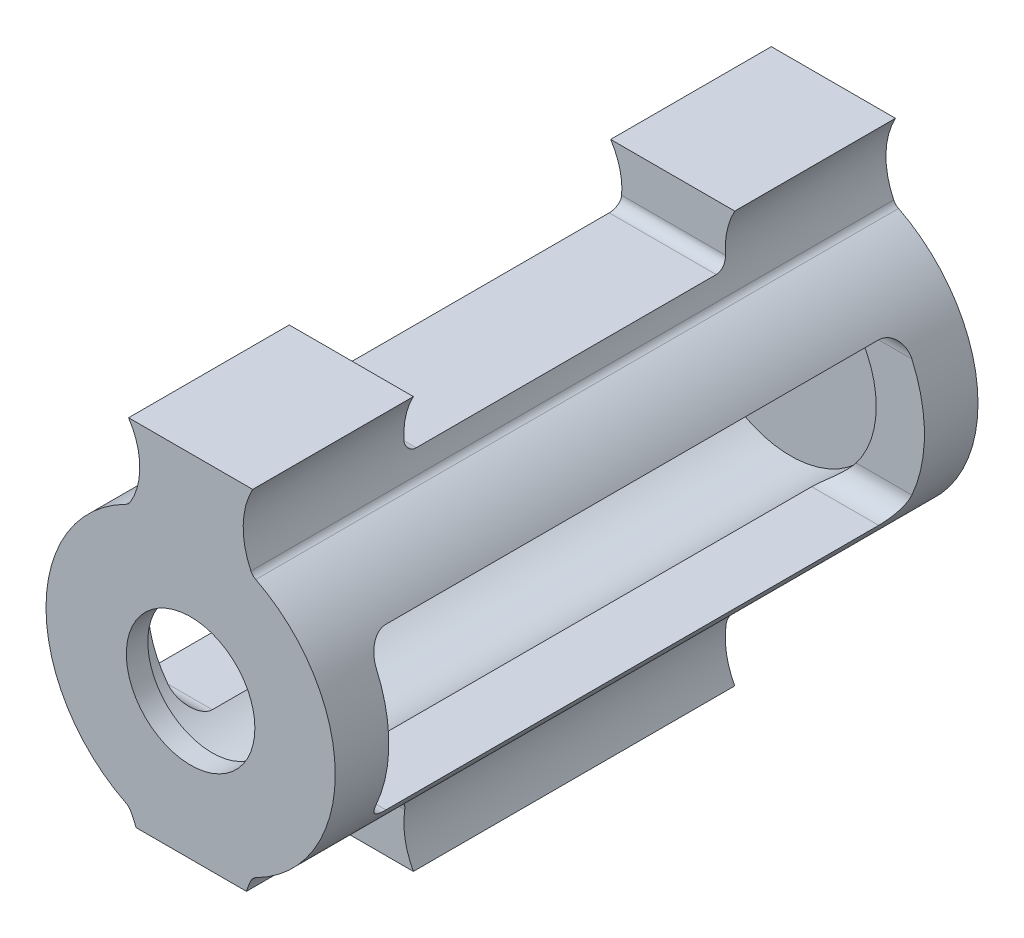
SolidWorks part; units mm, degrees
material "AISI 4130 Steel, annealed at 865C"
ref_plane "Front Plane" through (0, 0, 0) normal (0, 0, 1) x (1, 0, 0)
ref_plane "Top Plane" through (0, 0, 0) normal (0, 1, 0) x (1, 0, 0)
ref_plane "Right Plane" through (0, 0, 0) normal (1, 0, 0) x (0, 0, -1)
other "Center of Mass"
sketch "Sketch1" plane through (0, 0, 0) normal (0, 0, 1) x (1, 0, 0)
  line L8 (-34.29, 0) -> (-52.5688, 0)
  line L9 (-14.7129, 48.7531) -> (14.7129, 48.7531)
  line L10 (-14.7129, -48.7531) -> (14.7129, -48.7531)
  circle A0 centre (0, 0) radius 34.29
  circle A1 centre (0, 0) radius 22.86
  arc A2 (-14.7129, 48.7531) -> (-14.7129, 30.9731) centre (-28.2065, 39.8631) cw
  arc A3 (14.7129, 48.7531) -> (14.7129, 30.9731) centre (31.1324, 39.8631) ccw
  arc A4 (14.7129, -48.7531) -> (14.7129, -30.9731) centre (31.1324, -39.8631) cw
  arc A5 (-14.7129, -48.7531) -> (-14.7129, -30.9731) centre (-28.2065, -39.8631) ccw
  point P9 (0, 48.7531)
  dimension "D1" = 68.58
  dimension "D3" = 17.78
  dimension "D2" = 11.43
extrude "Boss-Extrude1" add sketch "Sketch1" along normal blind 139.7 and the other way blind 12.7 contours A3 L9 A2 A0 | A0 A1 | A5 L10 A4 A0 region at (0.1638, 41.1103, 0) region at (0, 33.3201, 0) region at (0.1638, -41.1103, 0)
ref_plane "Plane2" through (-14.7129, 0, 0) normal (1, 0, 0) x (0, 0, -1)
sketch "Sketch3" plane through (-14.7129, 0, 0) normal (1, 0, 0) x (0, 0, -1)
  line L5 (-25.4, 48.7531) -> (-25.4, 36.0531)
  line L6 (-25.4, 48.7531) -> (-101.6, 48.7531)
  line L7 (-25.4, 36.0531) -> (-101.6, 36.0531)
  line L8 (-101.6, 48.7531) -> (-101.6, 36.0531)
  line L9 (-139.7, 48.7531) -> (12.7, 48.7531) construction
  line L10 (-139.7, 30.9731) -> (12.7, 30.9731) construction
  line L11 (-101.6, -34.5291) -> (-139.7, -34.5291)
  line L12 (-139.7, -30.9731) -> (-139.7, -48.7531) construction
  line L13 (-139.7, -34.5291) -> (-139.7, -48.7531)
  line L14 (-139.7, -48.7531) -> (-101.6, -48.7531)
  line L15 (-139.7, -48.7531) -> (12.7, -48.7531) construction
  line L16 (-101.6, -48.7531) -> (-101.6, -34.5291)
  line L17 (-139.7, -30.9731) -> (12.7, -30.9731) construction
  line L18 (-63.5, 48.7531) -> (-63.5, 62.3768)
  line L19 (12.7, -34.5291) -> (12.7, -48.7531)
  line L20 (12.7, -48.7531) -> (-25.4, -48.7531)
  line L21 (-25.4, -48.7531) -> (-25.4, -34.5291)
  line L22 (-25.4, -34.5291) -> (12.7, -34.5291)
  dimension "D1" = 38.1
  dimension "D2" = 38.1
  dimension "D3" = 12.7
  dimension "D4" = 5.08
  dimension "D5" = 3.556
  dimension "D6" = 38.1
extrude "Cut-Extrude1" cut sketch "Sketch3" against normal through all both and the other way through all contours L6 L8 L7 L5 | L14 L16 L11 L13 | L22 L21 L20 L19 region at (-14.7129, 42.4031, 63.5) region at (-14.7129, -41.6411, 120.65) region at (-14.7129, -41.6411, 6.35)
fillet "Fillet1" radius 2.54 4 edges at (0.1752, 36.0531, 25.4) (0.1752, 36.0531, 101.6) (0.1427, -34.5291, 101.6) (0.1427, -34.5291, 25.4)
fillet "Fillet2" radius 2.54 4 edges at (-14.7129, 30.9731, 63.5) (14.7129, 30.9731, 63.5) (14.7129, -30.9731, 63.5) (-14.7129, -30.9731, 63.5)
sketch "Sketch5" plane through (-14.7129, 0, 0) normal (1, 0, 0) x (0, 0, -1)
  line L0 (-127, 19.05) -> (-127, -19.05)
  line L1 (-127, 19.05) -> (0, 19.05)
  line L2 (-127, -19.05) -> (0, -19.05)
  line L3 (0, 19.05) -> (0, -19.05)
  line L4 (-139.7, 30.6145) -> (-139.7, -30.6145) construction
  line L5 (12.7, -30.6145) -> (12.7, 30.6145) construction
  point P0 (0, 0)
  dimension "D1" = 12.7
  dimension "D2" = 38.1
  dimension "D3" = 12.7
extrude "Cut-Extrude2" cut sketch "Sketch5" against normal through all both and the other way through all
fillet "Fillet3" radius 5.08 7 edges at (20.5739, 19.05, 0) (20.5739, 19.05, 127) (20.5739, -19.05, 0) (20.5739, -19.05, 127) (-20.5739, -19.05, 127) (-20.5739, -19.05, 0) (-20.5739, 19.05, 0)
sketch "Sketch6" plane through (0, 0, -12.7) normal (0, 0, -1) x (-1, 0, 0)
  circle A0 centre (0, 0) radius 22.86 construction
  circle A1 centre (0, 0) radius 22.86
  circle A2 centre (0, 0) radius 5.08
  dimension "D1" = 10.16
extrude "Boss-Extrude2" add sketch "Sketch6" against normal blind 10.16
sketch "Sketch7" plane through (0, 0, 139.7) normal (0, 0, 1) x (1, 0, 0)
  circle A0 centre (0, 0) radius 22.86 construction
  circle A1 centre (0, 0) radius 22.86
  circle A2 centre (0, 0) radius 15.24
  dimension "D1" = 30.48
extrude "Boss-Extrude3" add sketch "Sketch7" against normal blind 5.08
